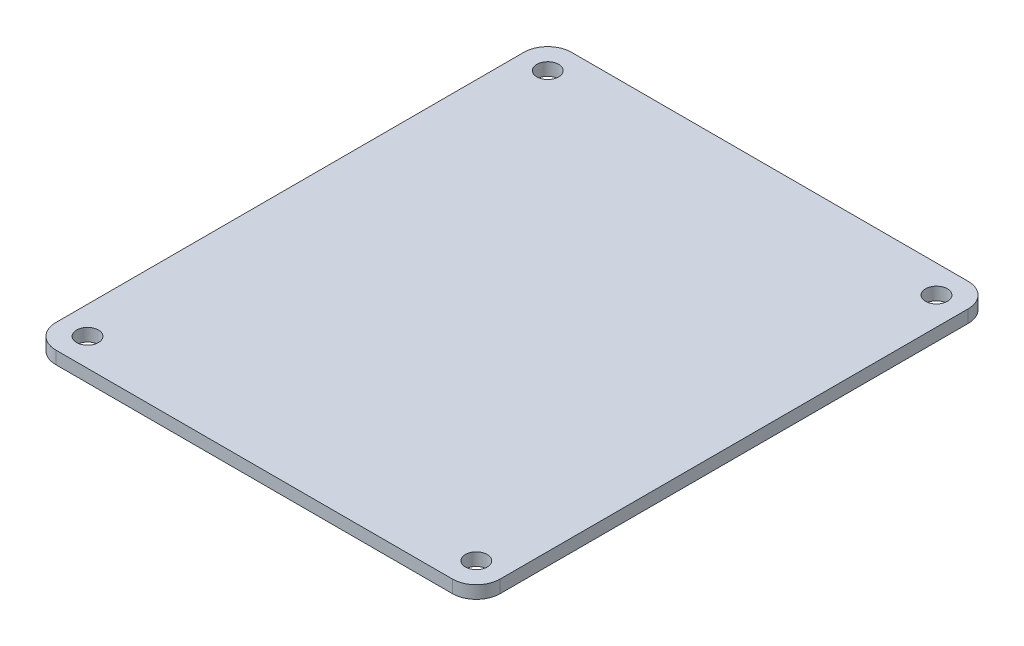
SolidWorks part; units mm, degrees
ref_plane "Front Plane" through (0, 0, 0) normal (0, 0, 1) x (1, 0, 0)
ref_plane "Top Plane" through (0, 0, 0) normal (0, 1, 0) x (1, 0, 0)
ref_plane "Right Plane" through (0, 0, 0) normal (1, 0, 0) x (0, 0, -1)
sketch "Sketch1" plane through (0, 0, 0) normal (0, 1, 0) x (1, 0, 0)
  line L1 (3, 0) -> (53, 0)
  line L2 (0, 3) -> (0, 62)
  line L3 (3, 65) -> (53, 65)
  line L4 (56, 3) -> (56, 62)
  arc A0 (0, 62) -> (3, 65) centre (3, 62) cw
  arc A1 (3, 0) -> (0, 3) centre (3, 3) cw
  arc A2 (53, 0) -> (56, 3) centre (53, 3) ccw
  arc A3 (53, 65) -> (56, 62) centre (53, 62) cw
  point P7 (0, 65)
  point P10 (0, 0)
  point P15 (56, 65)
  dimension "D3" = 3
  dimension "D1" = 65
  dimension "D2" = 56
extrude "Boss-Extrude1" add sketch "Sketch1" along normal blind 1.6002
hole_wizard "Ø2.7 (2.7) Diameter Hole1" positions "Sketch2" profile "Sketch3" hole size "Ø2.7" standard "ANSI Metric" end condition through all
sketch "Sketch2" plane through (0, 1.6002, 0) normal (0, 1, 0) x (1, 0, 0)
  line L0 (53, 65) -> (3, 65) construction
  line L1 (0, 62) -> (0, 3) construction
  point P0 (3.5, 61.5)
  point P2 (3.5, 3.5)
  point P9 (52.5, 61.5)
  point P11 (52.5, 3.5)
  dimension "D1" = 3.5
  dimension "D2" = 3.5
  dimension "D3" = 58
  dimension "D4" = 49
sketch "Sketch3" plane through (3.5, 1.6002, -61.5) normal (1, 0, 0) x (0, 0, 1)
  line L0 (0, 0) -> (0, 1.6002)
  line L1 (0, 1.6002) -> (1.375, 1.6002)
  line L2 (1.375, 1.6002) -> (1.375, 0)
  line L5 (1.375, 0) -> (0, 0)
  line L11 (0, -6.35) -> (0, 107.95) construction
  dimension "Thru Hole Dia." = 2.75
  dimension "Thru Hole Depth" = 1.6002
